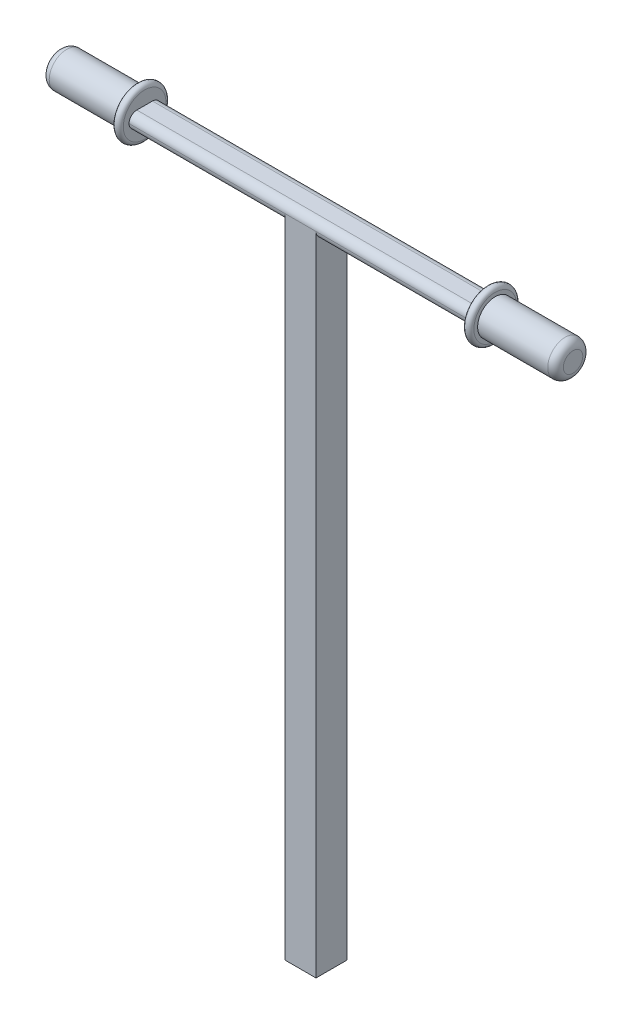
SolidWorks part; units mm, degrees
ref_plane "Front Plane" through (0, 0, 0) normal (0, 0, 1) x (1, 0, 0)
ref_plane "Top Plane" through (0, 0, 0) normal (0, 1, 0) x (1, 0, 0)
ref_plane "Right Plane" through (0, 0, 0) normal (1, 0, 0) x (0, 0, -1)
sketch "Sketch1" plane through (0, 0, 0) normal (0, 1, 0) x (1, 0, 0)
  line L1 (-20, 20) -> (20, 20)
  line L2 (-20, 20) -> (-20, -20)
  line L3 (-20, -20) -> (20, -20)
  line L4 (20, 20) -> (20, -20)
  line L5 (-20, 20) -> (20, -20) construction
  line L6 (-20, -20) -> (20, 20) construction
  point P0 (0, 0)
  dimension "D1" = 40
  dimension "D2" = 40
extrude "Boss-Extrude1" add sketch "Sketch1" along normal blind 290 and the other way blind 550
sketch "Sketch2" plane through (0, 0, 20) normal (0, 0, 1) x (1, 0, 0)
  line L0 (20, 290) -> (220, 290)
  line L1 (220, 290) -> (220, 270)
  line L2 (220, 270) -> (-220, 270)
  line L3 (-220, 270) -> (-220, 290)
  line L4 (-220, 290) -> (-20, 290)
  line L5 (-20, 290) -> (20, 290)
  dimension "D1" = 200
  dimension "D2" = 200
  dimension "D3" = 20
extrude "Boss-Extrude2" add sketch "Sketch2" against normal up to surface (40 mm away) up to face at (0, -130, -20)
sketch "Sketch3" plane through (220, 0, 0) normal (1, 0, 0) x (0, 0, -1)
  circle A1 centre (0, 280) radius 32.3607
extrude "Boss-Extrude3" add sketch "Sketch3" along normal blind 10
sketch "Sketch4" plane through (230, 0, 0) normal (1, 0, 0) x (0, 0, -1)
  circle A0 centre (0, 280) radius 22.5
  dimension "D1" = 45
extrude "Boss-Extrude4" add sketch "Sketch4" along normal blind 100
mirror "Mirror1" about plane through (0, 0, 0) normal (1, 0, 0) of "Boss-Extrude4", "Boss-Extrude3"
fillet "Fillet1" radius 10 6 edges at (-120, 270, -20) (120, 270, -20) (120, 270, 20) (-120, 270, 20) (0, 290, -20) (0, 290, 20)
fillet "Fillet2" 2 edges at (230, 312.3607, 0) (220, 312.3607, 0) type full round first side face at (230, 302.5, 0) second side face at (220, 280, 0) middle face at (230, 312.3607, 0)
fillet "Fillet3" 2 edges at (-220, 312.3607, 0) (-230, 312.3607, 0) type full round first side face at (-220, 280, 0) second side face at (-230, 302.5, 0) middle face at (-230, 312.3607, 0)
fillet "Fillet4" radius 10 2 edges at (-330, 302.5, 0) (330, 302.5, 0)
